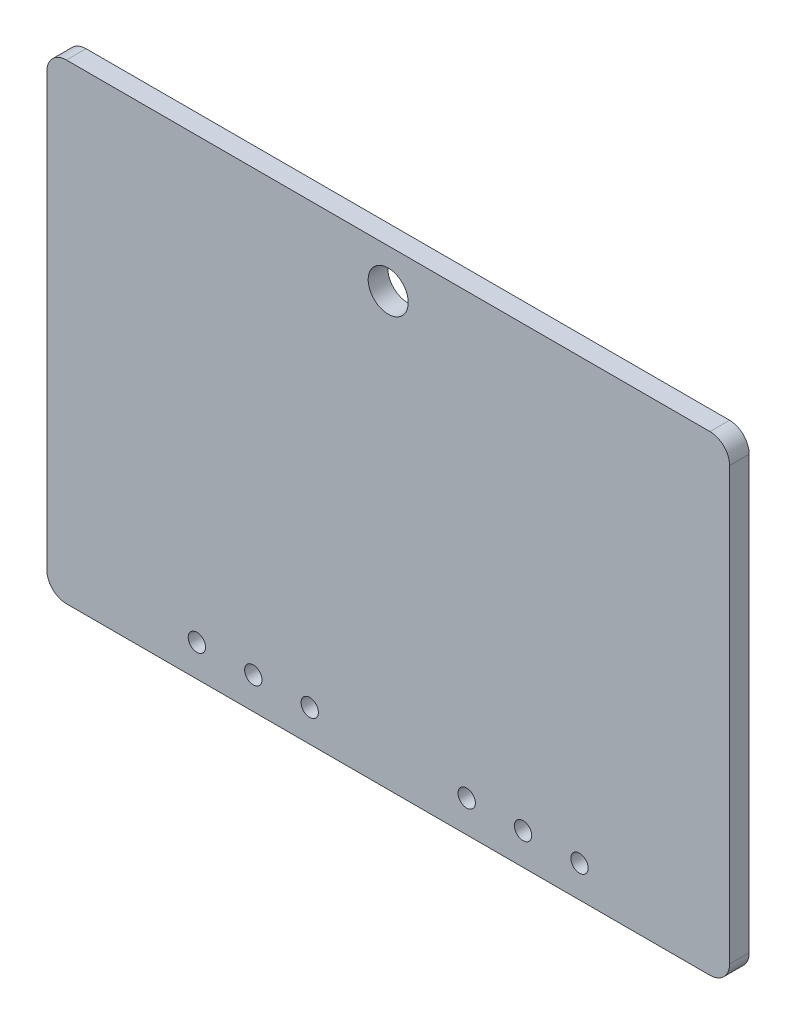
SolidWorks part; units mm, degrees
material "Acrylic (Medium-high impact)"
ref_plane "Front Plane" through (0, 0, 0) normal (0, 0, 1) x (1, 0, 0)
ref_plane "Top Plane" through (0, 0, 0) normal (0, 1, 0) x (1, 0, 0)
ref_plane "Right Plane" through (0, 0, 0) normal (1, 0, 0) x (0, 0, -1)
sketch "Sketch1" plane through (0, 0, 0) normal (0, 0, 1) x (1, 0, 0)
  line L1 (220.98, 152.4) -> (0, 152.4)
  line L2 (220.98, 152.4) -> (220.98, 0)
  line L3 (220.98, 0) -> (0, 0)
  line L4 (0, 152.4) -> (0, 0)
  line L5 (220.98, 152.4) -> (0, 0) construction
  line L6 (220.98, 0) -> (0, 152.4) construction
  point P0 (110.49, 76.2)
  dimension "D1" = 152.4
  dimension "D2" = 220.98
extrude "Boss-Extrude1" add sketch "Sketch1" along normal blind 6.35
hole_wizard "#10 Clearance Hole1" positions "Sketch6" profile "Sketch7" hole size "#10" standard "ANSI Inch" end condition through all
sketch "Sketch6" plane through (0, 0, 6.35) normal (0, 0, 1) x (1, 0, 0)
  line L2 (0, 0) -> (220.98, 0) construction
  line L3 (85.09, 10.3124) -> (135.89, 10.3124) construction
  line L5 (110.49, 0) -> (110.49, 10.3124) construction
  line L6 (48.5775, 10.3124) -> (85.09, 10.3124) construction
  line L9 (135.89, 10.3124) -> (172.4025, 10.3124) construction
  point P0 (48.5775, 10.3124)
  point P11 (85.09, 10.3124)
  point P13 (135.89, 10.3124)
  point P15 (172.4025, 10.3124)
  point P29 (66.8338, 10.3124)
  point P31 (154.1462, 10.3124)
  point P45 (66.8338, 10.3124)
  point P47 (154.1462, 10.3124)
  dimension "D1" = 36.5125
  dimension "D2" = 10.3124
  dimension "D5" = 50.8
sketch "Sketch7" plane through (48.5775, 10.3124, 6.35) normal (1, 0, 0) x (0, -1, 0)
  line L0 (0, 0) -> (0, 6.35)
  line L1 (0, 6.35) -> (2.8067, 6.35)
  line L2 (2.8067, 6.35) -> (2.8067, 0)
  line L5 (2.8067, 0) -> (0, 0)
  line L11 (0, -6.35) -> (0, 107.95) construction
  dimension "Thru Hole Dia." = 5.6134
  dimension "Thru Hole Depth" = 6.35
sketch "Sketch8" plane through (0, 0, 6.35) normal (0, 0, 1) x (1, 0, 0)
  line L0 (0, 0) -> (220.98, 0) construction
  line L1 (220.98, 152.4) -> (0, 152.4) construction
  circle A0 centre (110.49, 139.7) radius 6.477
  point P6 (110.49, 0)
  dimension "D1" = 12.954
  dimension "D2" = 12.7
extrude "Cut-Extrude1" cut sketch "Sketch8" against normal through all
fillet "Fillet1" radius 6.35 4 edges at (220.98, 0, 3.175) (220.98, 152.4, 3.175) (0, 152.4, 3.175) (0, 0, 3.175)
